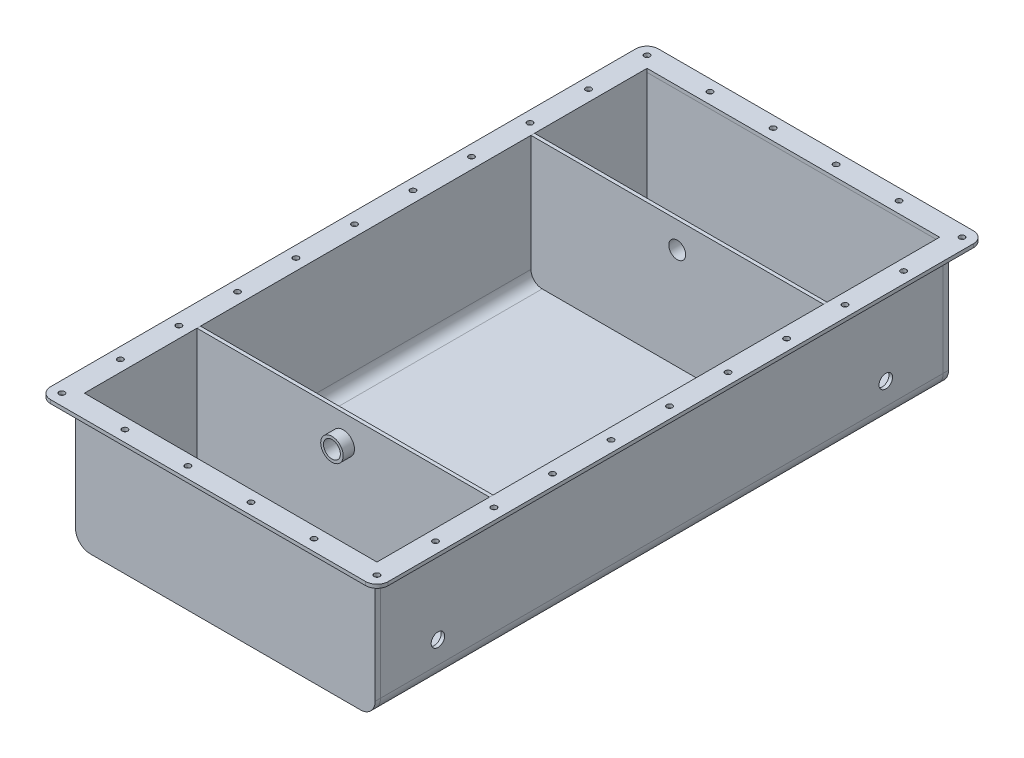
SolidWorks part; units mm, degrees
material "5052-H32"
ref_plane "Front Plane" through (0, 0, 0) normal (0, 0, 1) x (1, 0, 0)
ref_plane "Top Plane" through (0, 0, 0) normal (0, 1, 0) x (1, 0, 0)
ref_plane "Right Plane" through (0, 0, 0) normal (1, 0, 0) x (0, 0, -1)
sketch "Sketch2" plane through (0, 0, 0) normal (0, 0, 1) x (1, 0, 0)
  line L0 (-130, 0) -> (130, 0)
  line L1 (-130, 0) -> (-130, 110)
  line L2 (130, 0) -> (130, 110)
  line L3 (-133.175, -3.175) -> (-133.175, 110)
  line L4 (-133.175, -3.175) -> (133.175, -3.175)
  line L5 (133.175, -3.175) -> (133.175, 110)
  line L6 (-133.175, 110) -> (-130, 110)
  line L7 (130, 110) -> (133.175, 110)
  point P4 (0, 0)
  dimension "D1" = 260
  dimension "D3" = 110
  dimension "D4" = 110
  dimension "D2" = 3.175
  dimension "D5" = 3.175
  dimension "D6" = 3.175
extrude "Interior Dim" add sketch "Sketch2" against normal blind 500
fillet "Fillet2" radius 10 2 edges at (-130, 0, -250) (130, 0, -250)
fillet "Fillet3" radius 13.175 2 edges at (-133.175, -3.175, -250) (133.175, -3.175, -250)
ref_plane "Plane1" through (0, 0, 0) normal (0, 0, 1) x (1, 0, 0)
sketch "Sketch4" plane through (0, 0, 0) normal (0, 0, 1) x (1, 0, 0)
  line L0 (-130, 110) -> (130, 110)
  line L9 (-120, -3.175) -> (120, -3.175)
  line L10 (133.175, 10) -> (133.175, 110)
  line L11 (133.175, 110) -> (130, 110)
  line L12 (130, 110) -> (130, 10)
  line L13 (120, 0) -> (-120, 0)
  line L14 (-130, 10) -> (-130, 110)
  line L15 (-130, 110) -> (-133.175, 110)
  line L16 (-133.175, 110) -> (-133.175, 10)
  line L17 (-120, -3.175) -> (120, -3.175)
  line L18 (133.175, 10) -> (133.175, 110)
  line L19 (133.175, 110) -> (130, 110)
  line L23 (-130, 110) -> (-133.175, 110)
  line L24 (-133.175, 110) -> (-133.175, 10)
  arc A2 (120, 0) -> (130, 10) centre (120, 10) ccw
  arc A3 (-130, 10) -> (-120, 0) centre (-120, 10) ccw
  arc A13 (120, -3.175) -> (133.175, 10) centre (120, 10) ccw
  arc A14 (120, -3.175) -> (133.175, 10) centre (120, 10) ccw
  arc A16 (-133.175, 10) -> (-120, -3.175) centre (-120, 10) ccw
  arc A17 (-133.175, 10) -> (-120, -3.175) centre (-120, 10) ccw
  dimension "D1" = 0
extrude "Endcap1" add sketch "Sketch4" along normal blind 4.7625 separate body
ref_plane "Plane2" through (0, 0, -500) normal (0, 0, -1) x (-1, 0, 0)
sketch "Sketch5" plane through (0, 0, -500) normal (0, 0, -1) x (-1, 0, 0)
  line L8 (133.175, 110) -> (-133.175, 110)
  line L16 (-133.175, 110) -> (-133.175, 10)
  line L17 (-120, -3.175) -> (120, -3.175)
  line L18 (133.175, 10) -> (133.175, 110)
  line L19 (133.175, 110) -> (130, 110)
  line L20 (130, 110) -> (130, 10)
  line L21 (120, 0) -> (-120, 0)
  line L22 (-130, 10) -> (-130, 110)
  line L23 (-130, 110) -> (-133.175, 110)
  line L24 (-133.175, 110) -> (-133.175, 10)
  line L25 (-120, -3.175) -> (120, -3.175)
  line L26 (133.175, 10) -> (133.175, 110)
  arc A4 (120, 0) -> (130, 10) centre (120, 10) ccw
  arc A5 (-130, 10) -> (-120, 0) centre (-120, 10) ccw
  arc A17 (-133.175, 10) -> (-120, -3.175) centre (-120, 10) ccw
  arc A18 (-133.175, 10) -> (-120, -3.175) centre (-120, 10) ccw
  arc A19 (120, -3.175) -> (133.175, 10) centre (120, 10) ccw
  arc A20 (120, -3.175) -> (133.175, 10) centre (120, 10) ccw
  dimension "D1" = 0
ref_plane "Compartment1" through (0, 0, -100) normal (0, 0, -1) x (-1, 0, 0)
sketch "Sketch7" plane through (0, 0, -100) normal (0, 0, -1) x (-1, 0, 0)
  line L1 (130, 110) -> (-130, 110)
  line L10 (-120, -3.175) -> (120, -3.175)
  line L11 (-133.175, 110) -> (-133.175, 10)
  line L12 (-130, 110) -> (-133.175, 110)
  line L13 (-130, 10) -> (-130, 110)
  line L14 (120, 0) -> (-120, 0)
  line L15 (130, 110) -> (130, 10)
  line L16 (133.175, 110) -> (130, 110)
  line L17 (133.175, 10) -> (133.175, 110)
  line L21 (-130, 10) -> (-130, 110)
  line L22 (120, 0) -> (-120, 0)
  line L23 (130, 110) -> (130, 10)
  arc A2 (-130, 10) -> (-120, 0) centre (-120, 10) ccw
  arc A3 (-130, 10) -> (-120, 0) centre (-120, 10) ccw
  arc A6 (120, 0) -> (130, 10) centre (120, 10) ccw
  arc A7 (120, 0) -> (130, 10) centre (120, 10) ccw
  arc A12 (-133.175, 10) -> (-120, -3.175) centre (-120, 10) ccw
  arc A13 (120, -3.175) -> (133.175, 10) centre (120, 10) ccw
  dimension "D1" = 0
extrude "Compartment1_Boss" add sketch "Sketch7" along normal blind 3.175 separate body contours L22 A7 L23 L1 L21 A3 region at (0, 55.0793, -100)
ref_plane "Plane5" through (0, 110, 0) normal (0, 1, 0) x (1, 0, 0)
sketch "Sketch9" plane through (0, 110, 0) normal (0, 1, 0) x (1, 0, 0)
  line L0 (62.2463, 500) -> (-62.2463, 500) construction
  line L1 (-130, 500) -> (130, 500)
  line L2 (-130, 500) -> (-130, 0)
  line L3 (-130, 0) -> (130, 0)
  line L4 (130, 500) -> (130, 0)
  line L5 (-130, 0) -> (-130, 500) construction
  line L6 (-62.2463, 0) -> (62.2463, 0) construction
  line L7 (130, 500) -> (130, 0) construction
  line L8 (-150, 520) -> (-150, -20)
  line L9 (-150, -20) -> (150, -20)
  line L10 (150, 520) -> (150, -20)
  line L11 (-150, 520) -> (150, 520)
extrude "Lid_Flange" add sketch "Sketch9" along normal blind 3.175 separate body contours L11 L8 L9 L10 L1 L4 region at (0, 110, -513.8226)
fillet "Fillet4" radius 10 4 edges at (-150, 111.5875, -520) (150, 111.5875, -520) (150, 111.5875, 20) (-150, 111.5875, 20)
extrude "Endcap2" add sketch "Sketch5" along normal blind 4.7625 separate body
ref_plane "Compartment2" through (0, 0, -400) normal (0, 0, 1) x (1, 0, 0)
sketch "Sketch13" plane through (0, 0, -400) normal (0, 0, 1) x (1, 0, 0)
  line L0 (130, 110) -> (-130, 110)
  line L1 (133.175, 110) -> (130, 110) construction
  line L2 (130, 110) -> (130, 10) construction
  line L3 (-140, 110) -> (140, 110) construction
  line L4 (-130, 10) -> (-130, 110) construction
  line L5 (130, 110) -> (130, 10)
  line L6 (-130, 110) -> (-130, 10)
  line L7 (120, 0) -> (-120, 0)
  arc A0 (120, 0) -> (130, 10) centre (120, 10) ccw construction
  arc A1 (-130, 10) -> (-120, 0) centre (-120, 10) ccw construction
  arc A2 (-130, 10) -> (-120, 0) centre (-120, 10) ccw
  arc A3 (130, 10) -> (120, 0) centre (120, 10) cw
  dimension "D1" = 110
extrude "Compartment2_Boss" add sketch "Sketch13" along normal blind 3.175
sketch "Sketch16" plane through (-133.175, 0, 0) normal (-1, 0, 0) x (0, 0, 1)
  line L0 (-500, 0) -> (-400, 0) construction
  line L1 (-500, 110) -> (-500, 10) construction
  line L2 (0, 110) -> (0, 10) construction
  line L3 (-51, 29.5) -> (-449, 29.5) construction
  circle A0 centre (-449, 29.5) radius 6
  circle A1 centre (-51, 29.5) radius 6
  dimension "D1" = 12
  dimension "D4" = 12
  dimension "D2" = 29.5
  dimension "D3" = 51
  dimension "D5" = 51
extrude "Bearing_holes" cut sketch "Sketch16" against normal through all
sketch "Sketch17" plane through (0, 0, -400) normal (0, 0, -1) x (-1, 0, 0)
  line L0 (142.7388, 110) -> (-142.7388, 110) construction
  line L1 (130, 110) -> (130, 10) construction
  circle A0 centre (0, 90) radius 7.5
  circle A1 centre (0, 90) radius 10
  dimension "D1" = 15
  dimension "D4" = 20
  dimension "D3" = 130
extrude "Wire_Passthrough" cut sketch "Sketch17" against normal up to surface (300 mm away) contours A0 region at (0, 90, -400) up to face at (0, 39.3096, -100)
sketch "Sketch18" plane through (0, 110, 0) normal (0, 1, 0) x (1, 0, 0)
  line L1 (-130, 400) -> (130, 400)
  line L2 (-130, 400) -> (-130, 396.825)
  line L3 (-130, 396.825) -> (130, 396.825)
  line L4 (130, 400) -> (130, 396.825)
  line L5 (-130, 103.175) -> (130, 103.175)
  line L6 (-130, 103.175) -> (-130, 100)
  line L7 (-130, 100) -> (130, 100)
  line L8 (130, 103.175) -> (130, 100)
extrude "Boss-Extrude1" add sketch "Sketch18" along normal blind 3.18
extrude "Wire_Tube_2" add sketch "Sketch17<3>" along normal blind 10
sketch "Sketch17<3>" plane through (0, 0, -400) normal (0, 0, -1) x (-1, 0, 0) same geometry as "Sketch17"
sketch "Sketch19" plane through (0, 0, -100) normal (0, 0, 1) x (1, 0, 0)
  circle A0 centre (0, 90) radius 10
  circle M1 centre (0, 90) radius 7.5
  dimension "D1" = 20
extrude "Wire_Tube_1" add sketch "Sketch19" along normal blind 10 contours A0 M1 region at (-9.7172, 90, -100)
sketch "Sketch20" plane through (0, 110, 175) normal (0, 1, 0) x (1, 0, 0)
  line L0 (130, 425) -> (-130, 425) construction
  line L1 (-130, 675) -> (130, 675) construction
  line L2 (-130, 675) -> (-130, 175) construction
  line L3 (-130, 175) -> (130, 175) construction
  line L4 (130, 675) -> (130, 175) construction
  line L5 (130, 571.825) -> (130, 278.175) construction
  line L7 (0, 425) -> (0, 175) construction
  line L8 (-150, 695) -> (-150, 155) construction
  line L9 (-150, 155) -> (150, 155) construction
  line L10 (150, 695) -> (150, 155) construction
  line L11 (-150, 695) -> (150, 695) construction
  line L12 (-130, 571.825) -> (-130, 278.175) construction
  circle A0 centre (-140, 165) radius 2.5
  circle A2 centre (-140, 217) radius 2.5
  circle A3 centre (-140, 269) radius 2.5
  circle A4 centre (-140, 321) radius 2.5
  circle A5 centre (-140, 373) radius 2.5
  circle A6 centre (-140, 425) radius 2.5
  circle A7 centre (-140, 477) radius 2.5
  circle A8 centre (-140, 529) radius 2.5
  circle A9 centre (-140, 581) radius 2.5
  circle A10 centre (-140, 633) radius 2.5
  circle A16 centre (-140, 685) radius 2.5
  circle A17 centre (-84, 685) radius 2.5
  circle A18 centre (-28, 685) radius 2.5
  circle A19 centre (28, 685) radius 2.5
  circle A20 centre (84, 685) radius 2.5
  circle A21 centre (140, 685) radius 2.5
  circle A22 centre (140, 633) radius 2.5
  circle A23 centre (140, 581) radius 2.5
  circle A24 centre (140, 529) radius 2.5
  circle A25 centre (140, 477) radius 2.5
  circle A26 centre (140, 425) radius 2.5
  circle A27 centre (140, 373) radius 2.5
  circle A28 centre (140, 321) radius 2.5
  circle A29 centre (140, 269) radius 2.5
  circle A30 centre (140, 217) radius 2.5
  circle A31 centre (140, 165) radius 2.5
  circle A37 centre (84, 165) radius 2.5
  circle A38 centre (28, 165) radius 2.5
  circle A39 centre (-28, 165) radius 2.5
  circle A40 centre (-84, 165) radius 2.5
  dimension "D4" = 5
  dimension "D3" = 10
  dimension "D9" = 250
  dimension "D2" = 500
  dimension "D10" = 10
  dimension "D11" = 260
  dimension "D8" = 11
  dimension "D5" = 6
  dimension "D6" = 11
  dimension "D7" = 5
extrude "Bolt_Holes" cut sketch "Sketch20" along normal up to next
equation "\"L\"= 500"
equation "\"W\"= 260"
equation "\"D1@Sketch2\"=\"W\""
equation "\"D1@Interior Dim\" = \"L\""
equation "\"H\"= 110"
equation "\"D3@Sketch2\"=\"H\""
equation "\"D4@Sketch2\"=\"H\""
equation "\"Compartment Width\"= 100"
equation "\"D1@Compartment2\"=\"Compartment Width\""
equation "\"D1@Compartment1\"=\"Compartment Width\""
equation "\"D1@Sketch13\"=\"H\""
equation "\"D3@Sketch17\"=\"W\"/2"
equation "\"T\"= 4.7625 * 2 / 3"
equation "\"D1@Lid_Flange\"=\"T\""
equation "\"D1@Fillet3\"=\"T\"+10"
equation "\"D1@Compartment1_Boss\"=\"T\""
equation "\"D1@Compartment2_Boss\"=\"T\""
equation "\"D2@Sketch20\"=\"L\""
equation "\"D11@Sketch20\"=\"W\""
equation "\"D9@Sketch20\"=\"L\"/2"
